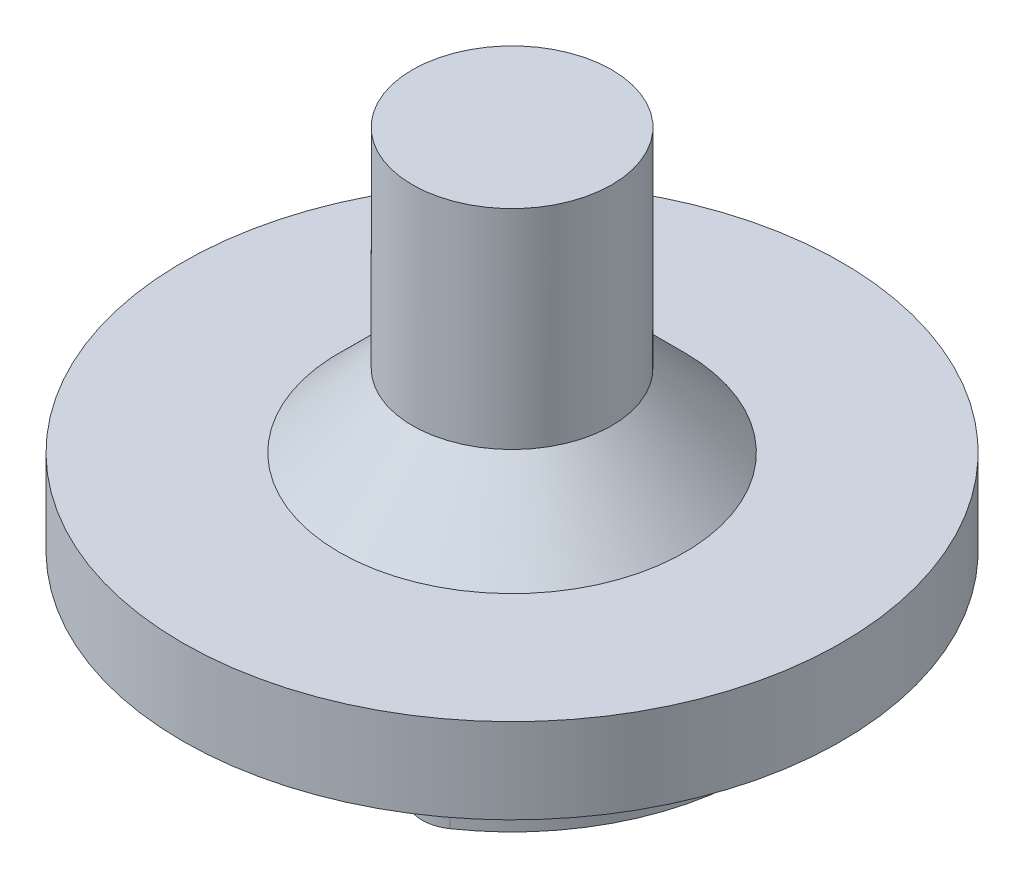
SolidWorks part; units mm, degrees
material "Caoutchouc naturel"
ref_plane "Plan de face" through (0, 0, 0) normal (0, 0, 1) x (1, 0, 0)
ref_plane "Plan de dessus" through (0, 0, 0) normal (0, 1, 0) x (1, 0, 0)
ref_plane "Plan de droite" through (0, 0, 0) normal (1, 0, 0) x (0, 0, -1)
sketch "Esquisse1" plane through (0, 0, 0) normal (0, 1, 0) x (1, 0, 0)
  circle A0 centre (0, 0) radius 6.2
  dimension "D1" = 12.4
extrude "Boss.-Extru.1" add sketch "Esquisse1" along normal blind 1.6
sketch "Esquisse2" plane through (0, 1.6, 0) normal (0, 1, 0) x (1, 0, 0)
  circle A0 centre (0, 0) radius 1.875
  dimension "D1" = 3.75
extrude "Boss.-Extru.3" add sketch "Esquisse2" along normal blind 5.3 contours A0
sketch "Esquisse3" plane through (0, 1.6, 0) normal (0, 1, 0) x (1, 0, 0)
  circle A0 centre (0, 0) radius 3.25
  dimension "D1" = 6.5
extrude "Boss.-Extru.5" add sketch "Esquisse3" along normal blind 1.8
chamfer "Chanfrein2" distance 1.8 angle 45 1 edges at (0, 3.4, 3.25)
sketch "Esquisse4" plane through (0, 0, 0) normal (0, -1, 0) x (1, 0, 0)
  circle A0 centre (0, 0) radius 4.5
  circle A1 centre (0, 0) radius 3.1
  arc A2 (3.7132, -2.5421) -> (0, -4.5) centre (0, 0) cw
  arc A3 (3.7132, -2.5421) -> (2.558, -1.7512) centre (3.1356, -2.1466) ccw
  arc A4 (0, -4.5) -> (0, -3.1) centre (0, -3.8) cw
  arc A5 (2.558, -1.7512) -> (0, -3.1) centre (0, 0) cw
  arc A6 (-1.7512, -2.558) -> (-3.1, 0) centre (0, 0) cw
  arc A7 (-4.5, 0) -> (-3.1, 0) centre (-3.8, 0) cw
  arc A8 (-2.5421, -3.7132) -> (-4.5, 0) centre (0, 0) cw
  arc A9 (-2.5421, -3.7132) -> (-1.7512, -2.558) centre (-2.1466, -3.1356) ccw
  arc A10 (-2.558, 1.7512) -> (0, 3.1) centre (0, 0) cw
  arc A11 (0, 4.5) -> (0, 3.1) centre (0, 3.8) cw
  arc A12 (-3.7132, 2.5421) -> (0, 4.5) centre (0, 0) cw
  arc A13 (-3.7132, 2.5421) -> (-2.558, 1.7512) centre (-3.1356, 2.1466) ccw
  arc A14 (1.7512, 2.558) -> (3.1, 0) centre (0, 0) cw
  arc A15 (4.5, 0) -> (3.1, 0) centre (3.8, 0) cw
  arc A16 (2.5421, 3.7132) -> (4.5, 0) centre (0, 0) cw
  arc A17 (2.5421, 3.7132) -> (1.7512, 2.558) centre (2.1466, 3.1356) ccw
  point P12 (-0.7, -3.8)
  point P13 (3.1356, -1.4466)
  point P35 (0, 0)
  dimension "D1" = 9
  dimension "D2" = 6.2
  dimension "D3" = 4.5
  dimension "D4" = 4
extrude "Boss.-Extru.6" add sketch "Esquisse4" along normal blind 1.4 contours A4 A0 A3 A1 | A0 A17 A1 A15 | A0 A9 A1 A7 | A0 A13 A1 A11 region at (3.1718, 0, 1.6724) region at (1.6724, 0, -3.1718) region at (-1.6724, 0, 3.1718) region at (-3.1718, 0, -1.6724)
